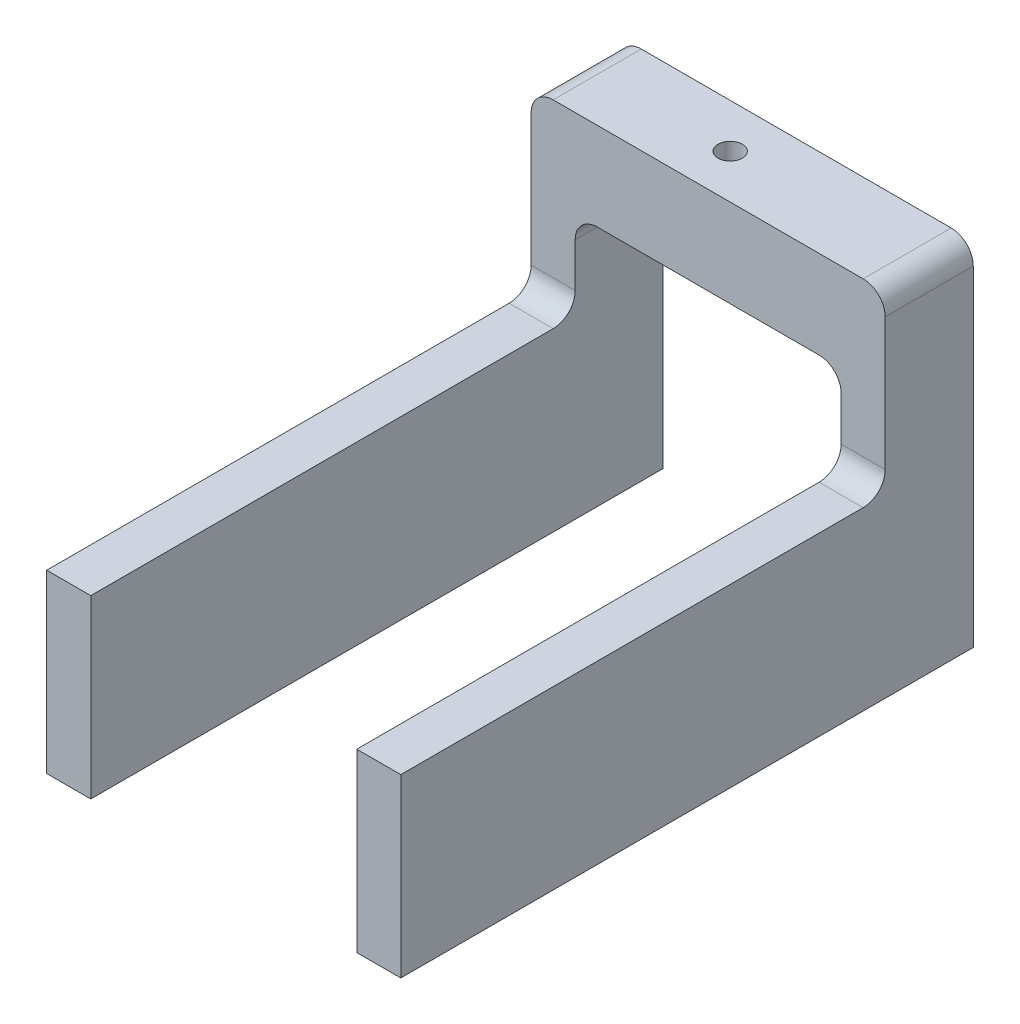
SolidWorks part; units mm, degrees
ref_plane "Front Plane" through (0, 0, 0) normal (0, 0, 1) x (1, 0, 0)
ref_plane "Top Plane" through (0, 0, 0) normal (0, 1, 0) x (1, 0, 0)
ref_plane "Right Plane" through (0, 0, 0) normal (1, 0, 0) x (0, 0, -1)
sketch "Sketch1" plane through (0, 0, 0) normal (1, 0, 0) x (0, 0, -1)
  line L0 (0, 0) -> (-165.1, 0)
  line L1 (-165.1, 0) -> (-165.1, 50.8)
  line L2 (-165.1, 50.8) -> (-25.4, 50.8)
  line L3 (-25.4, 50.8) -> (-25.4, 101.6)
  line L4 (-25.4, 101.6) -> (0, 101.6)
  line L5 (0, 101.6) -> (0, 0)
  point P7 (-12.7, 101.6)
  dimension "D1" = 152.4
  dimension "D2" = 50.8
  dimension "D3" = 101.6
  dimension "D4" = 25.4
extrude "Boss-Extrude1" add sketch "Sketch1" along normal blind 102.108
sketch "Sketch2" plane through (0, 0, 0) normal (0, 0, -1) x (-1, 0, 0)
  line L0 (-102.108, 0) -> (0, 0) construction
  line L1 (-89.408, 0) -> (-89.408, 76.2)
  line L2 (-89.408, 76.2) -> (-12.7, 76.2)
  line L3 (-12.7, 76.2) -> (-12.7, 0)
  line L4 (-12.7, 0) -> (-89.408, 0)
  line L5 (-102.108, 0) -> (-102.108, 101.6) construction
  line L6 (0, 0) -> (0, 101.6) construction
  line L7 (-102.108, 101.6) -> (0, 101.6) construction
  dimension "D1" = 12.7
  dimension "D2" = 12.7
  dimension "D3" = 25.4
extrude "Cut-Extrude1" cut sketch "Sketch2" against normal through all
hole_wizard "Ø7.0mm Dowel Hole1" positions "Sketch3" profile "Sketch4" hole size "Ø1.0" standard "ANSI Metric" end condition through all
sketch "Sketch3" plane through (0, 101.6, 0) normal (0, 1, 0) x (1, 0, 0)
  point P0 (44.704, -12.7)
  dimension "D1" = 44.704
  dimension "D2" = 12.7
sketch "Sketch4" plane through (44.704, 101.6, 12.7) normal (1, 0, 0) x (0, 0, 1)
  line L0 (0, 0) -> (0, 101.6)
  line L1 (0, 101.6) -> (3.5, 101.6)
  line L2 (3.5, 101.6) -> (3.5, 0)
  line L5 (3.5, 0) -> (0, 0)
  line L11 (0, -6.35) -> (0, 107.95) construction
  dimension "Thru Hole Dia." = 7
  dimension "Thru Hole Depth" = 101.6
fillet "Fillet1" radius 6.35 6 edges at (89.408, 76.2, 12.7) (12.7, 76.2, 12.7) (6.35, 50.8, 25.4) (95.758, 50.8, 25.4) (102.108, 101.6, 12.7) (0, 101.6, 12.7)
